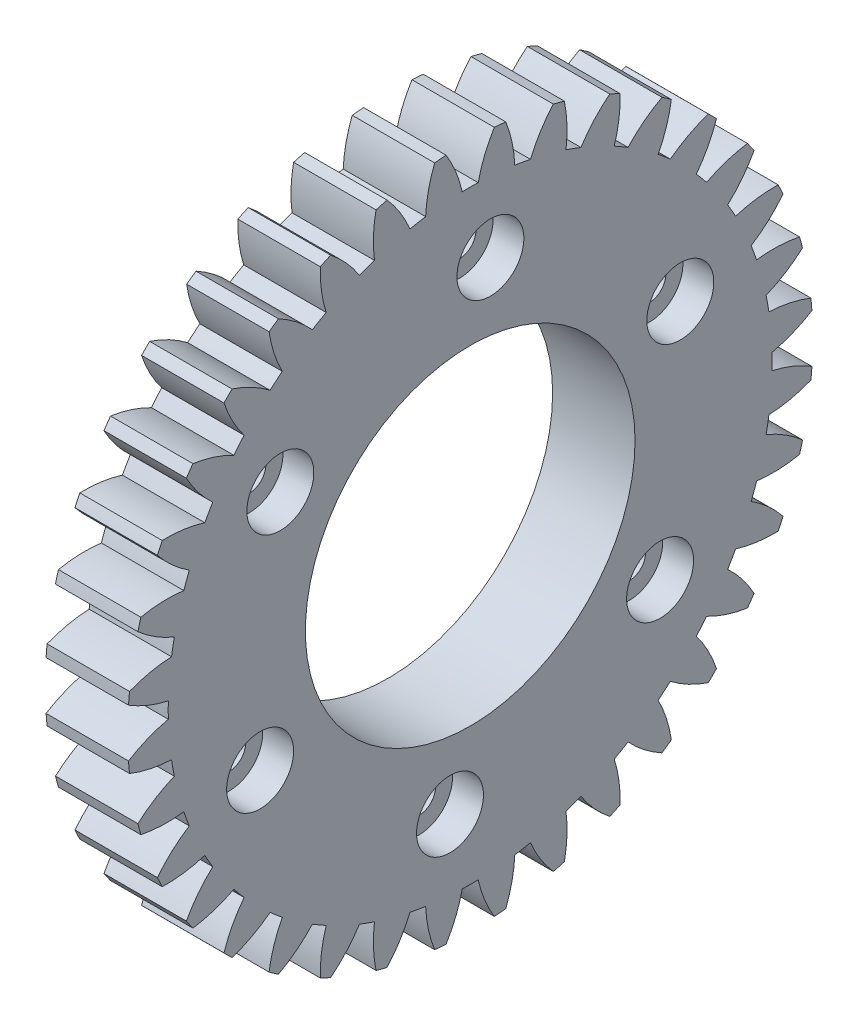
SolidWorks part; units mm, degrees
material "PLA personnalisé"
ref_plane "Plane1" through (0, 0, 0) normal (0, 0, 1) x (1, 0, 0)
ref_plane "Plane2" through (0, 0, 0) normal (0, 1, 0) x (1, 0, 0)
ref_plane "Plane3" through (0, 0, 0) normal (1, 0, 0) x (0, 0, -1)
other "Configuration Table"
sketch "HoldingSke" plane through (0, 0, 0) normal (0, 1, 0) x (1, 0, 0)
  line L0 (0, 0) -> (0.4623, -0.3359)
  line L1 (-15, 0) -> (100, 0) construction
  line L2 (0, 0) -> (-2.1039, 2.3779)
  line L3 (0, 0) -> (-11.863, 4.5341)
  line L4 (0, 0) -> (6.9867, 5.0761)
  line L5 (0, 0) -> (-46.8476, -17.4728)
  line L6 (0, 0) -> (-6.6317, -4.4744)
  line L7 (-2.1039, 2.3779) -> (8.6586, 51.2059)
  line L8 (-76.2, 54.61) -> (-74.8, 54.61)
  line L9 (-71.009, 38.7566) -> (-53.1078, 45.2721)
  line L10 (-76.2, 71.12) -> (104.1128, 71.12)
  line L11 (0, 0) -> (-8, 0)
  line L12 (-76.2, 101.6) -> (-76.147, 101.6)
  line L13 (24.9733, 27.94) -> (52.9518, 28.4284)
  line L14 (24.9733, 27.94) -> (24.9743, 27.94)
  line L15 (24.9733, 27.94) -> (100.4006, 29.5858)
  line L16 (-63.627, -1.75) -> (-12.827, -1.75)
  circle A0 centre (0, 0) radius 4
  circle A1 centre (0, 0) radius 29.3115
  circle A2 centre (0, 0) radius 37.5
  circle A3 centre (0, 0) radius 4
  dimension "MHD" = 58.623
  dimension "Hub_dia" = 75
  dimension "Bore" = 8
  dimension "MBD" = 8
  dimension "Num_teeth" = 36
  dimension "Pitch" = 0.5714
  dimension "Overall_len" = 50
  dimension "Show_teeth" = 36
  dimension "Thickness" = 8
  dimension "OAL" = 50.0001
  dimension "T_dim" = 1.4
  dimension "Ap" = 20
  dimension "H" = 19.05
  dimension "Pitch_radius" = 180.3128
  dimension "Width" = 8
  dimension "Backlash" = 0.053
  dimension "Addendum_fac" = 1
  dimension "Dedendum_fac" = 1.25
  dimension "Clearance_fac" = 0.25
  dimension "Dedendum_add" = 0.001
  dimension "Module" = 1.75
sketch "BasProSke" plane through (0, 0, 0) normal (0, 1, 0) x (1, 0, 0)
  line L0 (-10, 0) -> (60, 0) construction
  line L1 (0, 0) -> (0, 33.25)
  line L2 (0, 0) -> (8, 0)
  line L3 (8, 0) -> (8, 33.25)
  line L4 (8, 33.25) -> (0, 33.25)
  dimension "Thickness" = 8
  dimension "Diameter" = 66.5
revolve "Base-Revolve" add sketch "BasProSke" angle 360 about L0
sketch "TooCutSke" plane through (0, 0, 0) normal (1, 0, 0) x (0, 0, -1)
  line L1 (0, 0) -> (0, 107) construction
  line L2 (0, 0) -> (-1.4667, 31.4658) construction
  line L3 (0, 0) -> (-5.4863, 62.7083) construction
  line L4 (-1.4667, 31.4658) -> (-2.7431, 31.3542) construction
  arc A0 (0.7738, 29.3013) -> (-0.7738, 29.3013) centre (0, 0) ccw
  arc A1 (2.3593, 33.1917) -> (-2.3593, 33.1917) centre (0, 0) ccw
  circle A2 centre (0, 0) radius 31.5 construction
  circle A3 centre (0, 0) radius 29.6003 construction
  arc A4 (-0.7738, 29.3013) -> (-2.3593, 33.1917) centre (-13.0715, 26.5578) ccw
  arc A5 (2.3593, 33.1917) -> (0.7738, 29.3013) centre (13.0715, 26.5578) ccw
  dimension "Root_dia" = 58.623
  dimension "Overcut_dia" = 66.5508
  dimension "Pitch_dia" = 63
  dimension "Base_dia" = 59.2006
  dimension "Flank_rad" = 12.6
  dimension "Half_ang" = 5
  dimension "Half_CT" = 1.2813
extrude "ToothCut" cut sketch "TooCutSke" along normal through all
fillet "Breaks" [suppressed] radius 0.035 tangent propagation no
fillet "RootFillets" [suppressed] radius 0.4385
pattern_circular "TeethCuts" count 36 every 10 about axis through (-10, 0, 0) along (1, 0, 0) of "ToothCut", "RootFillets", "Breaks"
sketch "HubNeaOneSke" plane through (0, 0, 0) normal (-1, 0, 0) x (0, 0, 1)
  circle A0 centre (0, 0) radius 29.3115
  dimension "Diameter" = 58.623
extrude "HubNearOne" [suppressed] add sketch "HubNeaOneSke" along normal blind 42.0001
sketch "HubNeaBotSke" plane through (0, 0, 0) normal (-1, 0, 0) x (0, 0, 1)
  circle A0 centre (0, 0) radius 29.3115
  dimension "Diameter" = 58.623
extrude "HubNearBoth" [suppressed] add sketch "HubNeaBotSke" along normal blind 21
ref_plane "FarPln" through (8, 0, 0) normal (1, 0, 0) x (0, 0, -1)
sketch "HubFarSke" plane through (8, 0, 0) normal (1, 0, 0) x (0, 0, -1)
  circle A0 centre (0, 0) radius 29.3115
  dimension "Diameter" = 58.623
extrude "HubFar" [suppressed] add sketch "HubFarSke" along normal blind 21
sketch "BorSke" plane through (0, 0, 0) normal (1, 0, 0) x (0, 0, -1)
  circle A0 centre (0, 0) radius 4
  dimension "Diameter" = 8
extrude "Bore" cut sketch "BorSke" along normal mid plane 100.0001
sketch "KeySke" plane through (0, 0, 0) normal (1, 0, 0) x (0, 0, -1)
  line L0 (-1.5, 0) -> (-1.5, 5.4)
  line L1 (-1.5, 5.4) -> (1.5, 5.4)
  line L2 (1.5, 5.4) -> (1.5, 0)
  line L3 (0, 0) -> (0, 34) construction
  line L4 (-1.5, 0) -> (1.5, 0)
  dimension "Offset" = 5.4
  dimension "Width" = 3
extrude "Keyway" [suppressed] cut sketch "KeySke" along normal mid plane 100.0001
pattern_circular "Keyway2" [suppressed] count 2 every 90 about axis through (-10, 0, 0) along (1, 0, 0) reverse direction yes
sketch "Esquisse1" plane through (8, 0, 0) normal (1, 0, 0) x (0, 0, -1)
  circle A0 centre (0, 0) radius 16
  dimension "D1" = 32
extrude "Enlèv. mat.-Extru.1" cut sketch "Esquisse1" against normal blind 10
sketch "Esquisse2" plane through (8, 0, 0) normal (1, 0, 0) x (0, 0, -1)
  line L0 (2.8979, 33.1235) -> (0, 0) construction
  line L1 (1.3673, 15.6288) -> (2.5547, 29.2)
  arc A0 (3.4508, 33.0704) -> (2.3442, 33.1673) centre (0, 0) ccw construction
  circle A1 centre (0, 0) radius 29.3115
  circle A2 centre (0, 0) radius 15.6885
  circle A3 centre (1.961, 22.4144) radius 1.6
  circle A4 centre (0, 0) radius 22.5
  dimension "D1" = 3.2
  dimension "D2" = 45
extrude "Enlèv. mat.-Extru.2" cut sketch "Esquisse2" against normal blind 10 contours A3
sketch "Esquisse3" plane through (8, 0, 0) normal (1, 0, 0) x (0, 0, -1)
  circle A0 centre (1.961, 22.4144) radius 3.25
  dimension "D1" = 6.5
extrude "Enlèv. mat.-Extru.3" cut sketch "Esquisse3" against normal blind 3
pattern_circular "Répétition circulaire2" count 6 over 360 about axis through (8, 0, 0) along (1, 0, 0) of "Enlèv. mat.-Extru.3", "Enlèv. mat.-Extru.2"
equation "' \"Module@HoldingSke\" = 6.35"
equation "' \"Num_teeth@HoldingSke\" = 12"
equation "' \"Ap@HoldingSke\" =  20"
equation "' \"Ap@HoldingSke\" = 20"
equation "' \"Width@HoldingSke\" = 0.5 * 25.4"
equation "' \"Hub_dia@HoldingSke\"= 1 * 25.4"
equation "' \"Hub_dia@HoldingSke\" = 1 * 25.4"
equation "' \"Overall_len@HoldingSke\" = 1.0 * 25.4"
equation "' \"Bore@HoldingSke\" = 0.75 * 25.4"
equation "' \"T_dim@HoldingSke\" = 0.1 * 25.4"
equation "' \"Width@KeySke\" = 0.25 * 25.4"
equation "' \"Show_teeth@HoldingSke\" = 13"
equation "' \"Backlash@HoldingSke\" = 0.009 * 25.4"
equation "' \"Addendum_fac@HoldingSke\" = 1.0"
equation "' \"Dedendum_fac@HoldingSke\" = 1.25"
equation "' \"Dedendum_add@HoldingSke\" = 0.00005 * 25.4"
equation "' \"Clearance_fac@HoldingSke\" = 0.25"
equation "\"Pitch@HoldingSke\" = 1 / \"Module@HoldingSke\""
equation "\"Overcut_dia@TooCutSke\" = (\"Num_teeth@HoldingSke\" + 2 * \"Addendum_fac@HoldingSke\") / \"Pitch@HoldingSke\" + 0.002 * 25.4"
equation "\"Pitch_dia@TooCutSke\" = \"Num_teeth@HoldingSke\" / \"Pitch@HoldingSke\""
equation "\"Base_dia@TooCutSke\" = \"Num_teeth@HoldingSke\" / \"Pitch@HoldingSke\" * cos((\"Ap@HoldingSke\"  * 3.14159265 / 180))"
equation "\"Root_dia@TooCutSke\" = (\"Num_teeth@HoldingSke\" + 2) / \"Pitch@HoldingSke\" - 2 * (\"Addendum_fac@HoldingSke\" + \"Dedendum_fac@HoldingSke\") / \"Pitch@HoldingSke\" - \"Dedendum_add@HoldingSke\" * 2"
equation "\"Half_ang@TooCutSke\" = 180 / \"Num_teeth@HoldingSke\""
equation "\"Half_CT@TooCutSke\" = \"Num_teeth@HoldingSke\" / \"Pitch@HoldingSke\" * sin((3.14159265 / 2 / \"Num_teeth@HoldingSke\")) / 2 - 7 * \"Backlash@HoldingSke\" / 4"
equation "\"Flank_rad@TooCutSke\" = \"Num_teeth@HoldingSke\" / \"Pitch@HoldingSke\" / 5"
equation "\"Radius@RootFillets\" = \"Clearance_fac@HoldingSke\" / \"Pitch@HoldingSke\" + \"Dedendum_add@HoldingSke\""
equation "\"Break_rad@Breaks\" = 0.02 / \"Pitch@HoldingSke\""
equation "\"Thickness@HoldingSke\" = \"Width@HoldingSke\""
equation "\"OAL@HoldingSke\" = \"Thickness@HoldingSke\""
equation "\"MHD@HoldingSke\" = (\"Num_teeth@HoldingSke\" + 2) / \"Pitch@HoldingSke\" - 2 * (\"Addendum_fac@HoldingSke\" + \"Dedendum_fac@HoldingSke\")  / \"Pitch@HoldingSke\" - \"Dedendum_add@HoldingSke\" * 2"
equation "\"MBD@HoldingSke\" = (\"Num_teeth@HoldingSke\" + 2) / \"Pitch@HoldingSke\" - 2 * (\"Addendum_fac@HoldingSke\" + \"Dedendum_fac@HoldingSke\")  / \"Pitch@HoldingSke\" - \"Dedendum_add@HoldingSke\" * 2 - 0.002 * 25.4"
equation "\"MHD@HoldingSke\" = ((sgn( \"MHD@HoldingSke\" - \"Hub_dia@HoldingSke\" )-1)*( \"MHD@HoldingSke\" - \"Hub_dia@HoldingSke\" ))/-2+ \"Hub_dia@HoldingSke\""
equation "\"MBD@HoldingSke\" = ((sgn( \"MBD@HoldingSke\" - \"Bore@HoldingSke\" )-1)*( \"MBD@HoldingSke\" - \"Bore@HoldingSke\" ))/-2+ \"Bore@HoldingSke\""
equation "\"OAL@HoldingSke\" = ((sgn( \"OAL@HoldingSke\" - \"Overall_len@HoldingSke\" )+1)*( \"OAL@HoldingSke\" - \"Overall_len@HoldingSke\" ))/2 + \"Overall_len@HoldingSke\" + 0.000002 * 25.4"
equation "\"Num_teeth@TeethCuts\" = int( \"Show_teeth@HoldingSke\" ) + 1"
equation "\"Num_teeth@TeethCuts\" = ((sgn( \"Num_teeth@TeethCuts\" - \"Num_teeth@HoldingSke\" )-1)*( \"Num_teeth@TeethCuts\" - \"Num_teeth@HoldingSke\" ))/-2+ \"Num_teeth@HoldingSke\""
equation "\"Num_teeth@TeethCuts\" = ((sgn( \"Num_teeth@TeethCuts\" - 2.0)+1)*( \"Num_teeth@TeethCuts\" - 2.0))/2 +2.0"
equation "\"Angle@TeethCuts\" = 360.0 / \"Num_teeth@HoldingSke\""
equation "\"Diameter@BasProSke\" = (\"Num_teeth@HoldingSke\" + 2 * \"Addendum_fac@HoldingSke\") / \"Pitch@HoldingSke\""
equation "\"Thickness@BasProSke\"  = \"Thickness@HoldingSke\""
equation "' \"Fillet_rad@BasProSke\" =  \"Thickness@HoldingSke\" * 0.05"
equation "' \"Fillet_rad@BasProSke\" = \"Thickness@HoldingSke\" * 0.05"
equation "\"MHD@HoldingSke\" = ((sgn( \"MHD@HoldingSke\" - \"Root_dia@TooCutSke\" )-1)*( \"MHD@HoldingSke\" - \"Root_dia@TooCutSke\" ))/-2+ \"Root_dia@TooCutSke\""
equation "\"Diameter@HubNeaOneSke\" = \"MHD@HoldingSke\""
equation "\"Length@HubNearOne\" = \"OAL@HoldingSke\" - \"Thickness@BasProSke\""
equation "\"Diameter@HubNeaBotSke\" = \"MHD@HoldingSke\""
equation "\"Length@HubNearBoth\" = ( \"OAL@HoldingSke\" - \"Thickness@BasProSke\" ) / 2.0"
equation "\"Thickness@FarPln\" = \"Thickness@BasProSke\""
equation "\"Diameter@HubFarSke\" = \"MHD@HoldingSke\""
equation "\"Length@HubFar\" = ( \"OAL@HoldingSke\" - \"Thickness@BasProSke\" ) / 2.0"
equation "\"Diameter@BorSke\" = \"MBD@HoldingSke\""
equation "\"D1@Bore\" = \"OAL@HoldingSke\" * 2.0"
equation "\"D1@Keyway\" = \"OAL@HoldingSke\" * 2.0"
equation "\"Offset@KeySke\" = \"T_dim@HoldingSke\" + \"MBD@HoldingSke\" / 2.0"
